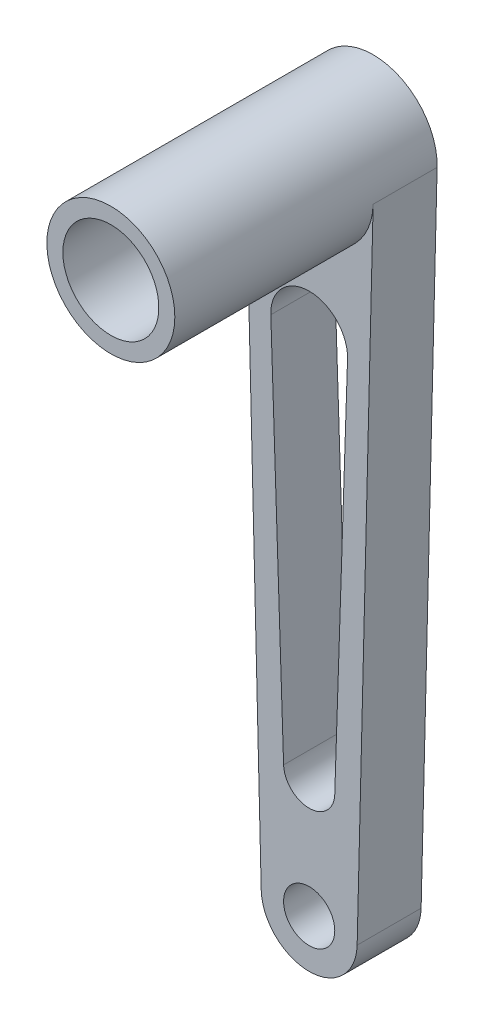
SolidWorks part; units mm, degrees
material "PEI"
ref_plane "Front Plane" through (0, 0, 0) normal (0, 0, 1) x (1, 0, 0)
ref_plane "Top Plane" through (0, 0, 0) normal (0, 1, 0) x (1, 0, 0)
ref_plane "Right Plane" through (0, 0, 0) normal (1, 0, 0) x (0, 0, -1)
sketch "Sketch1" plane through (0, 0, 0) normal (0, 0, 1) x (1, 0, 0)
  line L0 (-10.294, 11.8201) -> (-7.347, -107.9077)
  line L1 (0, -101.6) -> (0, 0) construction
  line L2 (7.347, -107.9067) -> (10.2653, 10.6574)
  line L3 (6.244, -15.7837) -> (3.867, -87.0546)
  line L4 (-6.2592, -15.3276) -> (-3.8401, -87.8596)
  circle A0 centre (0, 0) radius 10
  circle A1 centre (0, 0) radius 7.5
  circle A2 centre (0, -101.6) radius 7.5
  circle A3 centre (0, -101.6) radius 4
  circle A6 centre (0, -23) radius 6
  circle A7 centre (0, -83) radius 4
  point P19 (8.7502, -22.2008)
  point P20 (5.159, -17.845)
  point P21 (-2.8275, -63.8484)
  point P22 (0.5152, -82.7058)
  point P23 (-2.8839, -82.3943)
  point P24 (-6, -14)
  point P25 (6, -12.7226)
  point P26 (0, 0)
  point P27 (-3.8401, -84.8596)
  point P28 (4, -84.0546)
  point P29 (6.244, -12.7837)
  point P30 (-6.2592, -12.3276)
  dimension "D1" = 15
  dimension "D2" = 20
  dimension "D3" = 15
  dimension "D5" = 8
  dimension "D7" = 12
  dimension "D8" = 60
  dimension "D9" = 23
  dimension "D6" = 8
  dimension "D4" = 101.6
extrude "Boss-Extrude2" add sketch "Sketch1" along normal blind 10 contours L1 A2 L2 A0 | A2 L1 A0 L0 | A3 A2 region at (0, -11.0349, 0) region at (-0.0897, -94.3127, 0)
extrude "Boss-Extrude3" add sketch "Sketch1<6>" along normal blind 41 contours A0 A1 region at (-0.1196, 9.7164, 0)
sketch "Sketch1<6>" plane through (0, 0, 0) normal (0, 0, 1) x (1, 0, 0) same geometry as "Sketch1"
